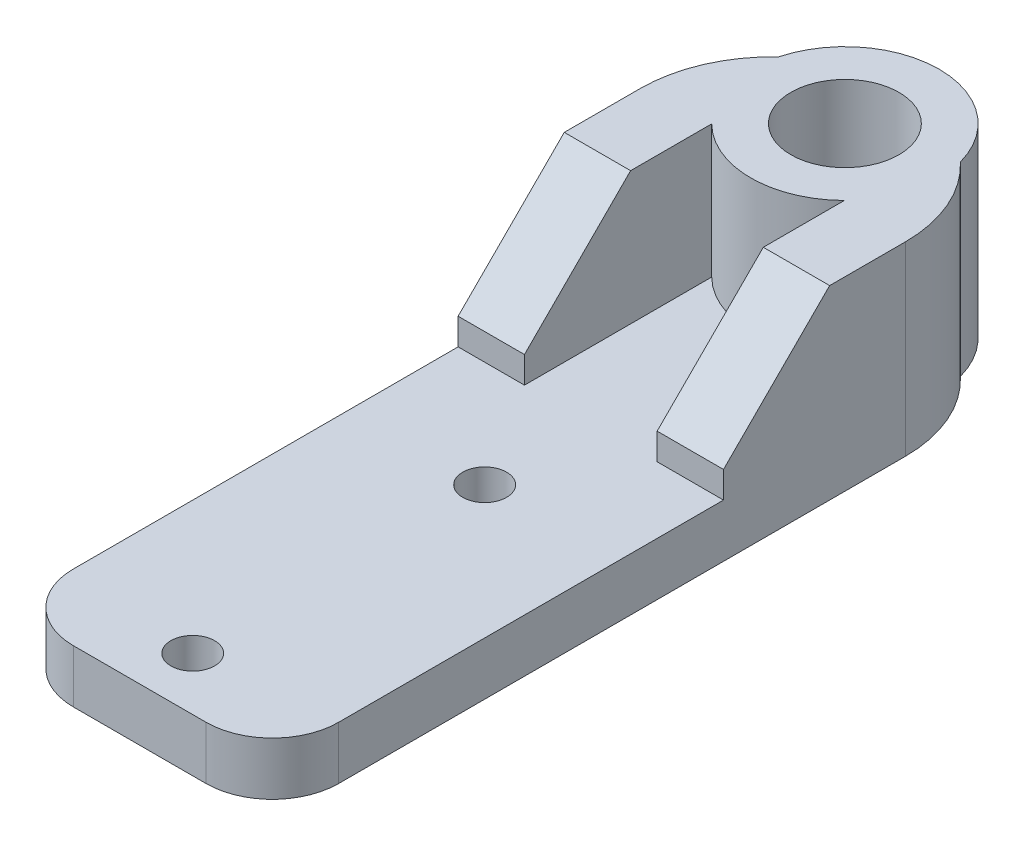
SolidWorks part; units mm, degrees
ref_plane "Front Plane" through (0, 0, 0) normal (0, 0, 1) x (1, 0, 0)
ref_plane "Top Plane" through (0, 0, 0) normal (0, 1, 0) x (1, 0, 0)
ref_plane "Right Plane" through (0, 0, 0) normal (1, 0, 0) x (0, 0, -1)
sketch "Sketch1" plane through (0, 0, 0) normal (0, 1, 0) x (1, 0, 0)
  line L1 (-10, -27.5) -> (10, -27.5)
  line L2 (-10, -27.5) -> (-10, 27.5)
  line L3 (-10, 27.5) -> (10, 27.5)
  line L4 (10, -27.5) -> (10, 27.5)
  line L5 (-10, -27.5) -> (10, 27.5) construction
  line L6 (-10, 27.5) -> (10, -27.5) construction
  point P0 (0, 0)
  dimension "D1" = 55
  dimension "D2" = 20
extrude "Boss-Extrude1" add sketch "Sketch1" along normal blind 4
sketch "Sketch2" plane through (0, 4, 0) normal (0, 1, 0) x (1, 0, 0)
  line L0 (0, 27.5) -> (0, 25.65) construction
  line L1 (10, 27.5) -> (-10, 27.5) construction
  line L2 (-10, -27.5) -> (10, -27.5) construction
  circle A0 centre (0, 25.65) radius 4.075
  dimension "D1" = 8.15
  dimension "D2" = 53.15
extrude "Cut-Extrude1" cut sketch "Sketch2" against normal through all both and the other way through all
sketch "Sketch3" plane through (0, 4, 0) normal (0, 1, 0) x (1, 0, 0)
  circle A0 centre (0, 25.65) radius 7.1
  circle A1 centre (0, 25.65) radius 4.075 construction
  circle A2 centre (0, 25.65) radius 4.075
  dimension "D1" = 14.2
extrude "Boss-Extrude2" add sketch "Sketch3" along normal blind 10 and the other way up to surface (4 mm away) other way up to face at (0, 0, -8.1792)
sketch "Sketch4" plane through (10, 0, 0) normal (1, 0, 0) x (0, 0, -1)
  line L0 (32.75, 14) -> (18.55, 14) construction
  line L1 (27.5, 0) -> (6.5, 0)
  line L2 (27.5, 0) -> (27.5, 14)
  line L3 (27.5, 14) -> (6.5, 14)
  line L4 (6.5, 0) -> (6.5, 14)
  point P5 (0, 0)
  dimension "D1" = 21
extrude "Boss-Extrude3" add sketch "Sketch4" against normal blind 5
chamfer "Chamfer1" distance 8 angle 45 1 edges at (7.5, 14, -6.5)
mirror "Mirror1" about plane through (0, 0, 0) normal (1, 0, 0) of "Boss-Extrude3", "Chamfer1"
fillet "Fillet3" radius 10 2 edges at (10, 7, -27.5) (-10, 7, -27.5)
fillet "Fillet4" radius 5 2 edges at (10, 2, 27.5) (-10, 2, 27.5)
sketch "Sketch5" plane through (0, 4, 0) normal (0, 1, 0) x (1, 0, 0)
  line L0 (0, -27.5) -> (0, -1.5) construction
  line L1 (-5, -27.5) -> (5, -27.5) construction
  circle A0 centre (0, -23.5) radius 1.65
  circle A1 centre (0, -1.5) radius 1.65
  dimension "D2" = 3.3
  dimension "D1" = 4
  dimension "D3" = 22
extrude "Cut-Extrude2" cut sketch "Sketch5" against normal through all
